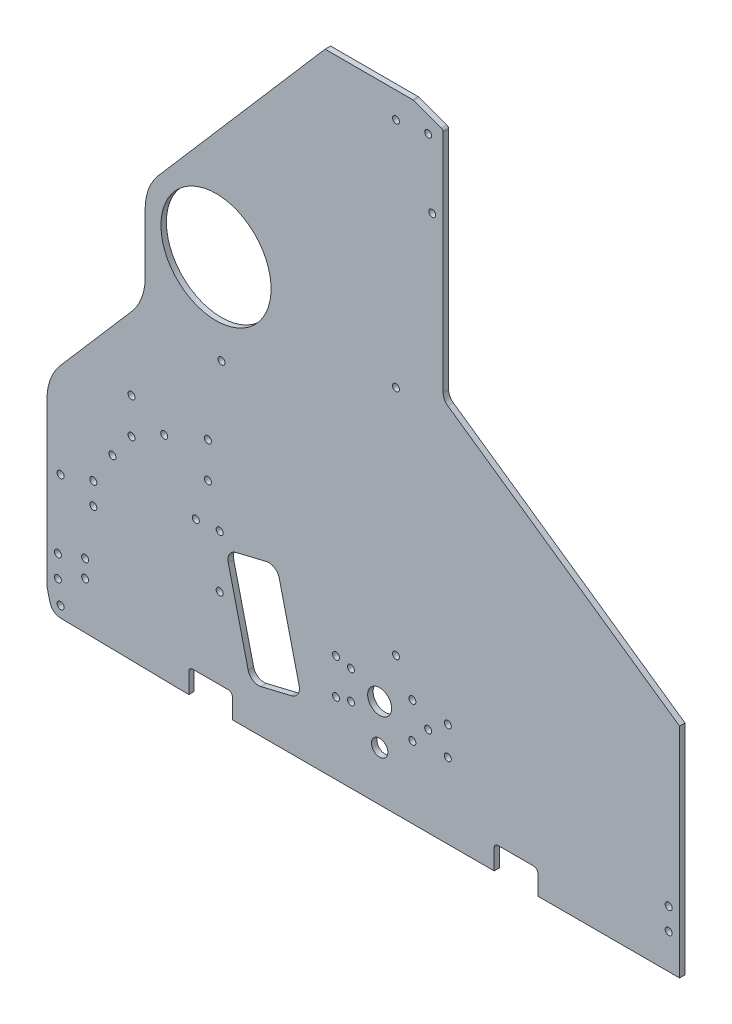
SolidWorks part; units mm, degrees
ref_plane "Front Plane" through (0, 0, 0) normal (0, 0, 1) x (1, 0, 0)
ref_plane "Top Plane" through (0, 0, 0) normal (0, 1, 0) x (1, 0, 0)
ref_plane "Right Plane" through (0, 0, 0) normal (1, 0, 0) x (0, 0, -1)
sketch "Sketch1" plane through (0, 0, 0) normal (0, 0, 1) x (1, 0, 0)
  line L0 (82.55, -20.32) -> (82.55, -6.35)
  line L2 (0, 0) -> (0, 157.48)
  line L4 (368.3, -20.32) -> (368.3, 106.68)
  line L5 (82.55, -6.35) -> (107.95, -6.35)
  line L6 (107.95, -6.35) -> (107.95, -20.32)
  line L7 (107.95, -20.32) -> (260.35, -20.32)
  line L8 (260.35, -20.32) -> (260.35, -6.35)
  line L9 (260.35, -6.35) -> (285.75, -6.35)
  line L10 (285.75, -6.35) -> (285.75, -20.32)
  line L11 (285.75, -20.32) -> (368.3, -20.32)
  line L12 (361.95, 12.7) -> (368.3, 12.7) construction
  line L13 (0, 0) -> (6.35, 0) construction
  line L14 (0.1896, -7.8901) -> (1.7771, -14.2401)
  line L15 (7.8295, -19.0491) -> (82.55, -20.32)
  line L16 (0, 0) -> (0, -6.35)
  line L17 (68.2625, 103.505) -> (71.4375, 103.505) construction
  line L18 (49.2125, 93.1863) -> (93.6625, 93.1862) construction
  line L19 (49.2125, 93.1863) -> (49.2125, 113.8238) construction
  line L20 (93.6625, 93.1862) -> (93.6625, 113.8237) construction
  line L21 (49.2125, 113.8238) -> (93.6625, 113.8237) construction
  line L22 (49.2125, 93.1863) -> (93.6625, 113.8237) construction
  line L23 (93.6625, 93.1862) -> (49.2125, 113.8238) construction
  line L24 (7.9375, -12.7) -> (86.6784, 70.1514) construction
  line L25 (203.2, 59.805) -> (203.2, 194.805) construction
  line L26 (203.2, 194.805) -> (203.2, 329.805) construction
  line L27 (355.6, 332.105) -> (330.2, 332.105) construction
  line L28 (330.2, 332.105) -> (330.2, 217.805) construction
  line L29 (330.2, 217.805) -> (355.6, 217.805) construction
  line L30 (355.6, 217.805) -> (355.6, 332.105) construction
  line L31 (203.2, 344.805) -> (203.2, 194.805) construction
  line L32 (50.8, 332.105) -> (76.2, 332.105) construction
  line L33 (76.2, 332.105) -> (76.2, 217.805) construction
  line L34 (50.8, 217.805) -> (50.8, 332.105) construction
  line L35 (76.2, 217.805) -> (50.8, 217.805) construction
  line L36 (213.2, 344.805) -> (230.6638, 338.455)
  line L37 (203.2, 344.805) -> (161.925, 344.805)
  line L38 (203.2, 344.805) -> (213.2, 344.805)
  line L39 (348.5362, 344.805) -> (413.4623, 344.805)
  line L40 (348.5362, 344.805) -> (230.6638, 344.805) construction
  line L42 (161.925, 344.805) -> (0, 157.48)
  line L44 (230.6638, 338.455) -> (230.6638, 202.565)
  line L45 (230.6638, 202.565) -> (368.3, 106.68)
  line L46 (213.2, 344.805) -> (-141.0713, 344.805) construction
  circle A0 centre (6.35, 0) radius 2.032
  circle A1 centre (6.35, 12.7) radius 2.032
  circle A2 centre (361.95, 0) radius 2.032
  circle A3 centre (361.95, 12.7) radius 2.032
  arc A5 (1.7771, -14.2401) -> (7.8295, -19.0491) centre (7.9375, -12.7) ccw
  circle A6 centre (7.9375, -12.7) radius 2.032
  arc A7 (0, -6.35) -> (0.1896, -7.8901) centre (6.35, -6.35) ccw
  circle A8 centre (38.1, 78.105) radius 2.032
  circle A9 centre (68.2625, 103.505) radius 2.032
  circle A10 centre (93.6625, 93.1862) radius 2.032
  circle A11 centre (93.6625, 113.8237) radius 2.032
  circle A12 centre (49.2125, 113.8238) radius 2.032
  circle A13 centre (49.2125, 93.1863) radius 2.032
  circle A14 centre (86.6784, 70.1514) radius 2.032
  circle A15 centre (203.2, 59.805) radius 2
  circle A16 centre (203.2, 194.805) radius 2
  circle A17 centre (203.2, 329.805) radius 2
  circle A18 centre (63.5, 313.055) radius 2.032
  circle A19 centre (101.6, 157.48) radius 2.032
  circle A20 centre (355.6, 332.105) radius 2.032
  circle A21 centre (330.2, 332.105) radius 2.032
  circle A22 centre (355.6, 217.805) radius 2.032
  circle A23 centre (330.2, 217.805) radius 2.032
  circle A24 centre (50.8, 332.105) radius 2.032
  circle A25 centre (76.2, 332.105) radius 2.032
  circle A26 centre (50.8, 217.805) radius 2.032
  circle A27 centre (76.2, 217.805) radius 2.032
  circle A28 centre (221.9319, 332.105) radius 2
  circle A29 centre (224.3138, 293.243) radius 2.032
  point P82 (203.2, 344.805)
  point P83 (221.9319, 341.63)
  dimension "D6" = 4.064
  dimension "D10" = 6.35
  dimension "D11" = 4.064
  dimension "D17" = 38.1
  dimension "D27" = 4
  dimension "D31" = 4.064
  dimension "D32" = 41.275
  dimension "D36" = 4.064
  dimension "D47" = 45.212
  dimension "D48" = 4.064
  dimension "D2" = 127
  dimension "D3" = 13.97
  dimension "D4" = 25.4
  dimension "D5" = 152.4
  dimension "D7" = 12.7
  dimension "D8" = 6.35
  dimension "D9" = 20.32
  dimension "D12" = 12.7
  dimension "D13" = 1.5875
  dimension "D14" = 82.55
  dimension "D15" = 368.3
  dimension "D16" = 6.35
  dimension "D18" = 98.425
  dimension "D19" = 30.1625
  dimension "D20" = 25.4
  dimension "D21" = 3.175
  dimension "D22" = 270
  dimension "D23" = 20.6375
  dimension "D24" = 44.45
  dimension "D25" = 38.1
  dimension "D26" = 114.3
  dimension "D28" = 135
  dimension "D29" = 12.7
  dimension "D30" = 15
  dimension "D33" = 63.5
  dimension "D34" = 27.4638
  dimension "D35" = 101.6
  dimension "D37" = 114.3
  dimension "D38" = 25.4
  dimension "D39" = 12.7
  dimension "D40" = 157.48
  dimension "D41" = 142.24
  dimension "D42" = 365.125
  dimension "D43" = 10
  dimension "D44" = 6.35
  dimension "D45" = 31.75
  dimension "D46" = 6.35
  dimension "D49" = 6.35
  dimension "D50" = 203.2
extrude "Boss-Extrude1" add sketch "Sketch1" along normal blind 3.175 contours L16 A7 L14 A5 L15 L2 A0 A1 A6 region at (171.4242, 119.663, 0)
fillet "Fillet1" radius 2.286 4 edges at (285.75, -6.35, 1.5875) (107.95, -6.35, 1.5875) (260.35, -6.35, 1.5875) (82.55, -6.35, 1.5875)
fillet "Fillet2" radius 6.35 1 edges at (230.6638, 202.565, 1.5875)
sketch "Sketch2" plane through (0, 0, 0) normal (0, 0, -1) x (-1, 0, 0)
  circle A0 centre (-100.5528, 71.086) radius 2.032 construction
  circle A1 centre (-100.5528, 40.606) radius 2.032 construction
  circle A2 centre (-22.225, 18.2025) radius 2.032 construction
  circle A3 centre (-22.225, 8.0425) radius 2.032 construction
  circle A4 centre (-100.5528, 71.086) radius 2.032
  circle A5 centre (-100.5528, 40.606) radius 2.032
  circle A6 centre (-22.225, 18.2025) radius 2.032
  circle A7 centre (-22.225, 8.0425) radius 2.032
extrude "Cut-Extrude1" cut sketch "Sketch2" against normal through all
fillet "Fillet3" radius 1.5875 2 edges at (230.6638, 338.455, 1.5875) (213.2, 344.805, 1.5875)
sketch "Sketch3" plane through (0, 0, 3.175) normal (0, 0, 1) x (1, 0, 0)
  line L0 (132.9524, 63.2646) -> (132.7215, 64.2281) construction
  line L1 (128.3815, 66.8897) -> (110.6829, 62.6472) construction
  line L2 (114.5132, 58.4237) -> (126.8822, 61.3887) construction
  line L3 (108.0212, 58.3071) -> (108.2522, 57.3436) construction
  line L4 (131.2006, 57.703) -> (140.0164, 20.9265) construction
  line L5 (144.0993, 16.7636) -> (132.9524, 63.2646) construction
  line L6 (108.2522, 57.3436) -> (119.3991, 10.8426) construction
  line L7 (121.1509, 16.4042) -> (112.3351, 53.1807) construction
  line L8 (119.3991, 10.8426) -> (119.6301, 9.8791) construction
  line L9 (144.3303, 15.8001) -> (144.0993, 16.7636) construction
  line L10 (137.8383, 15.6835) -> (125.4694, 12.7185) construction
  line L11 (123.9701, 7.2175) -> (141.6687, 11.4601) construction
  line L12 (132.9524, 63.2646) -> (132.7215, 64.2281)
  line L13 (128.3815, 66.8897) -> (110.6829, 62.6472)
  line L14 (114.5132, 58.4237) -> (126.8822, 61.3887)
  line L15 (108.0212, 58.3071) -> (108.2522, 57.3436)
  line L16 (131.2006, 57.703) -> (140.0164, 20.9265)
  line L17 (144.0993, 16.7636) -> (132.9524, 63.2646)
  line L18 (108.2522, 57.3436) -> (119.3991, 10.8426)
  line L19 (121.1509, 16.4042) -> (112.3351, 53.1807)
  line L20 (119.3991, 10.8426) -> (119.6301, 9.8791)
  line L21 (144.3303, 15.8001) -> (144.0993, 16.7636)
  line L22 (137.8383, 15.6835) -> (125.4694, 12.7185)
  line L23 (123.9701, 7.2175) -> (141.6687, 11.4601)
  line L24 (127.7894, 69.3598) -> (110.0908, 65.1172)
  line L25 (105.5512, 57.715) -> (105.7822, 56.7515)
  line L26 (105.7822, 56.7515) -> (116.9291, 10.2505)
  line L27 (116.9291, 10.2505) -> (117.1601, 9.287)
  line L28 (124.5622, 4.7475) -> (142.2608, 8.99)
  line L29 (146.8003, 16.3922) -> (146.5694, 17.3557)
  line L30 (146.5694, 17.3557) -> (135.4225, 63.8567)
  line L31 (135.4225, 63.8567) -> (135.1915, 64.8202)
  arc A0 (132.7215, 64.2281) -> (128.6308, 66.9403) centre (129.2207, 63.3889) ccw construction
  arc A1 (110.6829, 62.6472) -> (110.4377, 62.5791) centre (111.5221, 59.1463) ccw construction
  arc A2 (128.6308, 66.9403) -> (128.3815, 66.8897) centre (129.2207, 63.3889) ccw construction
  arc A3 (110.4377, 62.5791) -> (108.0212, 58.3071) centre (111.5221, 59.1463) ccw construction
  arc A4 (119.6301, 9.8791) -> (123.7207, 7.1669) centre (123.1309, 10.7183) ccw construction
  arc A5 (141.9139, 11.5281) -> (144.3303, 15.8001) centre (140.8295, 14.9609) ccw construction
  arc A6 (141.6687, 11.4601) -> (141.9139, 11.5281) centre (140.8295, 14.9609) ccw construction
  arc A7 (123.7207, 7.1669) -> (123.9701, 7.2175) centre (123.1309, 10.7183) ccw construction
  arc A8 (132.7215, 64.2281) -> (128.6308, 66.9403) centre (129.2207, 63.3889) ccw
  arc A9 (110.6829, 62.6472) -> (110.4377, 62.5791) centre (111.5221, 59.1463) ccw
  arc A10 (128.6308, 66.9403) -> (128.3815, 66.8897) centre (129.2207, 63.3889) ccw
  arc A11 (110.4377, 62.5791) -> (108.0212, 58.3071) centre (111.5221, 59.1463) ccw
  arc A12 (119.6301, 9.8791) -> (123.7207, 7.1669) centre (123.1309, 10.7183) ccw
  arc A13 (141.9139, 11.5281) -> (144.3303, 15.8001) centre (140.8295, 14.9609) ccw
  arc A14 (141.6687, 11.4601) -> (141.9139, 11.5281) centre (140.8295, 14.9609) ccw
  arc A15 (123.7207, 7.1669) -> (123.9701, 7.2175) centre (123.1309, 10.7183) ccw
  arc A16 (110.0908, 65.1172) -> (109.6726, 65.0012) centre (111.5221, 59.1463) ccw
  arc A17 (109.6726, 65.0012) -> (105.5512, 57.715) centre (111.5221, 59.1463) ccw
  arc A18 (117.1601, 9.287) -> (124.1369, 4.6613) centre (123.1309, 10.7183) ccw
  arc A19 (124.1369, 4.6613) -> (124.5622, 4.7475) centre (123.1309, 10.7183) ccw
  arc A20 (142.2608, 8.99) -> (142.679, 9.1061) centre (140.8295, 14.9609) ccw
  arc A21 (142.679, 9.1061) -> (146.8003, 16.3922) centre (140.8295, 14.9609) ccw
  arc A22 (135.1915, 64.8202) -> (128.2147, 69.446) centre (129.2207, 63.3889) ccw
  arc A23 (128.2147, 69.446) -> (127.7894, 69.3598) centre (129.2207, 63.3889) ccw
  circle A30 centre (26.9875, 46.9531) radius 2.032 construction
  circle A31 centre (26.9875, 59.6531) radius 2.032 construction
  circle A32 centre (7.9375, 53.3031) radius 2.032 construction
  circle A33 centre (26.9875, 46.9531) radius 2.032
  circle A34 centre (26.9875, 59.6531) radius 2.032
  circle A35 centre (7.9375, 53.3031) radius 2.032
  ellipse E0 centre (124.5975, 48.8487) end of major axis (128.5376, 61.3578) minor radius 6 (131.2006, 57.703) -> (126.8822, 61.3887) ccw construction
  ellipse E1 centre (122.235, 48.2824) end of major axis (113.0518, 57.6456) minor radius 6 (114.5132, 58.4237) -> (112.3351, 53.1807) ccw construction
  ellipse E2 centre (127.7541, 25.2585) end of major axis (131.6942, 37.7675) minor radius 6 (121.1509, 16.4042) -> (125.4694, 12.7185) ccw construction
  ellipse E3 centre (130.1166, 25.8248) end of major axis (139.2998, 16.4616) minor radius 6 (137.8383, 15.6835) -> (140.0164, 20.9265) ccw construction
  ellipse E4 centre (124.5975, 48.8487) end of major axis (128.5376, 61.3578) minor radius 6 (131.2006, 57.703) -> (126.8822, 61.3887) ccw
  ellipse E5 centre (122.235, 48.2824) end of major axis (131.4181, 38.9192) minor radius 6 (114.5132, 58.4237) -> (112.3351, 53.1807) ccw
  ellipse E6 centre (127.7541, 25.2585) end of major axis (123.814, 12.7495) minor radius 6 (121.1509, 16.4042) -> (125.4694, 12.7185) ccw
  ellipse E7 centre (130.1166, 25.8248) end of major axis (139.2998, 16.4616) minor radius 6 (137.8383, 15.6835) -> (140.0164, 20.9265) ccw
  dimension "D1" = 2.54
extrude "Cut-Extrude2" cut sketch "Sketch3" against normal through all contours A22 A23 L24 A16 A17 L25 L26 L27 A18 A19 L28 A20 A21 L29 L30 L31 A15 A12 L20 L18 L15 A11 A9 L13 A10 A8 L12 L17 L21 A13 A14 L23 | A12 A15 L23 A14 A13 L21 L17 L12 A8 A10 L13 A9 A11 L15 L18 L20 E7 L22 E6 L19 E5 L14 E4 L16 | L22 E7 L16 E4 L14 E5 L19 E6 | A35 | A34 | A33 region at (137.844, 39.8506, 3.175) region at (126.1758, 37.0536, 3.175) region at (128.1544, 68.6507, 3.175)
sketch "Sketch4" plane through (0, 0, 3.175) normal (0, 0, 1) x (1, 0, 0)
  line L0 (49.2125, 113.8238) -> (93.6625, 113.8237) construction
  line L1 (168.275, 21.4312) -> (212.725, 21.4312) construction
  line L2 (168.275, 21.4312) -> (168.275, 42.0687) construction
  line L3 (168.275, 42.0687) -> (212.725, 42.0687) construction
  line L4 (212.725, 21.4312) -> (212.725, 42.0687) construction
  line L5 (168.275, 21.4312) -> (212.725, 42.0687) construction
  line L6 (168.275, 42.0687) -> (212.725, 21.4312) construction
  line L7 (49.2125, 93.1863) -> (49.2125, 113.8238) construction
  line L8 (107.95, -20.32) -> (260.35, -20.32) construction
  line L9 (193.675, 31.75) -> (177.005, 31.75) construction
  line L10 (190.5, 31.75) -> (193.675, 31.75) construction
  line L11 (6.35, 12.7) -> (361.95, 12.7) construction
  line L12 (107.95, -6.35) -> (107.95, -20.32) construction
  line L13 (193.675, 31.75) -> (220.6625, 31.75) construction
  line L14 (177.005, 23.4569) -> (177.005, 40.0431) construction
  line L15 (213.2, 44.805) -> (193.2, 44.805) construction
  line L16 (213.2, 44.805) -> (213.2, 344.805) construction
  line L17 (213.2, 344.805) -> (193.2, 344.805) construction
  line L18 (193.2, 44.805) -> (193.2, 344.805) construction
  line L19 (213.2, 44.805) -> (193.2, 344.805) construction
  line L20 (213.2, 344.805) -> (193.2, 44.805) construction
  line L21 (226.9319, 332.105) -> (226.9319, 31.75) construction
  line L22 (237.33, 40.0431) -> (233.3612, 40.0431) construction
  line L23 (237.33, 23.4569) -> (233.3612, 23.4569) construction
  circle A0 centre (168.275, 42.0687) radius 2.032
  circle A1 centre (212.725, 42.0687) radius 2.032
  circle A2 centre (212.725, 21.4312) radius 2.032
  circle A3 centre (168.275, 21.4312) radius 2.032
  circle A4 centre (193.675, 31.75) radius 6.985
  circle A7 centre (220.6625, 31.75) radius 14.2875 construction
  circle A8 centre (193.675, 31.75) radius 12.7 construction
  circle A9 centre (177.005, 40.0431) radius 2.032
  circle A10 centre (177.005, 23.4569) radius 2.032
  circle A11 centre (237.33, 40.0431) radius 2.032 construction
  circle A12 centre (237.33, 23.4569) radius 2.032 construction
  circle A13 centre (193.675, 8.4667) radius 4.7625
  circle A14 centre (221.9319, 31.75) radius 2.032
  circle A15 centre (221.9319, 31.75) radius 5 construction
  circle A16 centre (221.9319, 332.105) radius 5 construction
  circle A17 centre (233.3612, 23.4569) radius 2.032
  circle A18 centre (233.3612, 40.0431) radius 2.032
  point P0 (190.5, 31.75)
  point P26 (203.2, 194.805)
  point P38 (177.005, 31.75)
  dimension "D1" = 4.064
  dimension "D4" = 13.97
  dimension "D7" = 9.525
  dimension "D10" = 25.4
  dimension "D11" = 28.575
  dimension "D16" = 10
  dimension "D17" = 4.064
  dimension "D18" = 10
  dimension "D2" = 52.07
  dimension "D3" = 3.175
  dimension "D5" = 82.55
  dimension "D6" = 26.9875
  dimension "D8" = 20
  dimension "D9" = 300
  dimension "D12" = 16.67
  dimension "D13" = 16.5862
  dimension "D14" = 60.325
  dimension "D15" = 23.2833
  dimension "D19" = 3.9688
extrude "Cut-Extrude3" cut sketch "Sketch4" against normal through all
sketch "Sketch5" plane through (0, 0, -187.325) normal (0, 0, -1) x (-1, 0, 0)
  line L0 (-57.15, 223.5947) -> (-57.15, 165.3337)
  line L1 (-161.925, 344.805) -> (-52.7201, 218.4699) construction
  line L2 (-57.15, 165.3337) -> (0, 99.219)
  line L3 (0, -6.35) -> (0, 157.48) construction
  line L4 (-50.4199, 215.8089) -> (0, 157.48) construction
  line L5 (-50.4199, 215.8089) -> (0, 157.48) construction
  line L6 (-57.15, 223.5947) -> (0, 157.48)
  line L7 (0, 157.48) -> (0, 99.219)
  circle A0 centre (-98.425, 208.2281) radius 32.0675
  dimension "D3" = 64.135
  dimension "D1" = 38.1
  dimension "D2" = 57.15
  dimension "D4" = 41.275
  dimension "D5" = 41.275
extrude "Cut-Extrude5" cut sketch "Sketch5" against normal through all contours A0 | L7 L6 L0 L2 region at (28.575, 161.4068, -187.325) region at (98.425, 208.2281, -187.325)
fillet "Fillet4" radius 31.75 3 edges at (0, 99.219, 1.5875) (57.15, 165.3337, 1.5875) (57.15, 223.5947, 1.5875)
